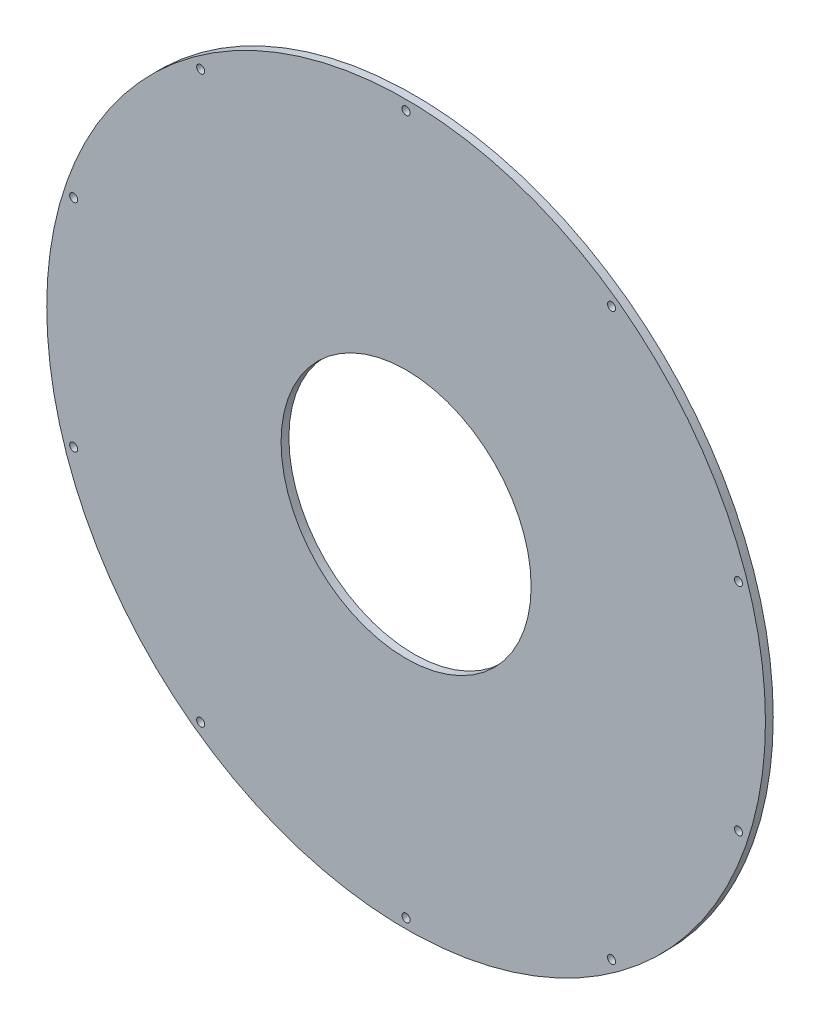
SolidWorks part; units mm, degrees
material "PET"
ref_plane "Front Plane" through (0, 0, 0) normal (0, 0, 1) x (1, 0, 0)
ref_plane "Top Plane" through (0, 0, 0) normal (0, 1, 0) x (1, 0, 0)
ref_plane "Right Plane" through (0, 0, 0) normal (1, 0, 0) x (0, 0, -1)
sketch "Sketch1" plane through (0, 0, 0) normal (0, 0, 1) x (1, 0, 0)
  circle A0 centre (0, 0) radius 146
  circle A1 centre (0, 0) radius 50.8
  dimension "D1" = 292
  dimension "D2" = 101.6
extrude "Boss-Extrude1" add sketch "Sketch1" along normal blind 3.175
hole_wizard "#4 Clearance Hole1" positions "Sketch3" profile "Sketch2" hole size "#4" standard "Ansi Inch" end condition through all
sketch "Sketch3" plane through (0, 0, 3.175) normal (0, 0, 1) x (1, 0, 0)
  point P0 (0, 142)
  dimension "D1" = 142
sketch "Sketch2" plane through (0, 142, 3.175) normal (1, 0, 0) x (0, -1, 0)
  line L0 (0, 0) -> (0, 3.175)
  line L1 (0, 3.175) -> (1.6319, 3.175)
  line L2 (1.6319, 3.175) -> (1.6319, 0)
  line L5 (1.6319, 0) -> (0, 0)
  line L11 (0, -6.35) -> (0, 107.95) construction
  dimension "Thru Hole Dia." = 3.2639
  dimension "Thru Hole Depth" = 3.175
pattern_circular "CirPattern1" count 10 over 360 about axis through (0, 0, 3.175) along (0, 0, -1) of "#4 Clearance Hole1"
